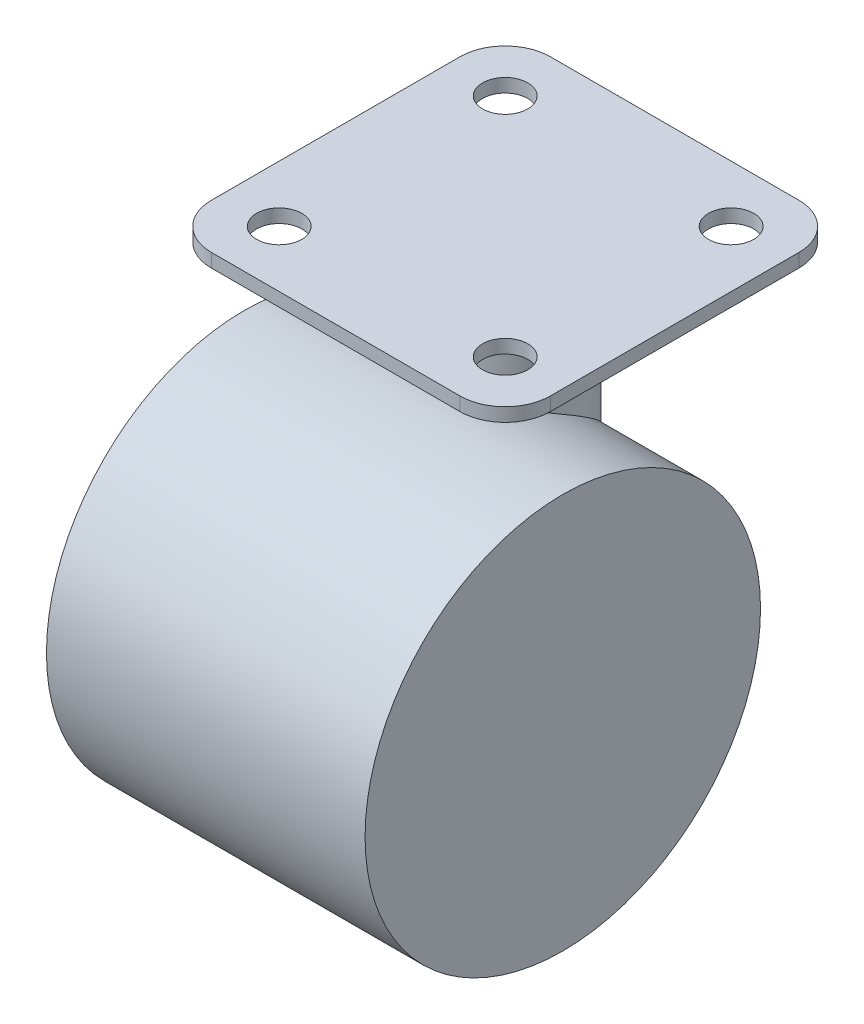
SolidWorks part; units mm, degrees
ref_plane "Спереди" through (0, 0, 0) normal (0, 0, 1) x (1, 0, 0)
ref_plane "Сверху" through (0, 0, 0) normal (0, 1, 0) x (1, 0, 0)
ref_plane "Справа" through (0, 0, 0) normal (1, 0, 0) x (0, 0, -1)
sketch "Эскиз1" plane through (0, 0, 0) normal (0, 1, 0) x (1, 0, 0)
  line L1 (-15, -15) -> (15, -15)
  line L2 (-15, -15) -> (-15, 15)
  line L3 (-15, 15) -> (15, 15)
  line L4 (15, -15) -> (15, 15)
  line L5 (-15, -15) -> (15, 15) construction
  line L6 (-15, 15) -> (15, -15) construction
  point P0 (0, 0)
  dimension "D2" = 30
extrude "основание" add sketch "Эскиз1" against normal mid plane 1.2
sketch "Эскиз7" plane through (0, 0.6, 0) normal (0, 1, 0) x (1, 0, 0)
  line L1 (-10, -10) -> (10, -10) construction
  line L2 (-10, -10) -> (-10, 10) construction
  line L3 (-10, 10) -> (10, 10) construction
  line L4 (10, -10) -> (10, 10) construction
  line L5 (-10, -10) -> (10, 10) construction
  line L6 (-10, 10) -> (10, -10) construction
  circle A0 centre (-10, 10) radius 2
  circle A1 centre (10, 10) radius 2
  circle A2 centre (10, -10) radius 2
  circle A3 centre (-10, -10) radius 2
  point P0 (0, 0)
  dimension "D1" = 4
  dimension "D2" = 20
  dimension "D3" = 20
extrude "крепженые отверстия" cut sketch "Эскиз7" against normal through all
fillet "Скругление4" radius 4 4 edges at (15, 0, -15) (15, 0, 15) (-15, 0, 15) (-15, 0, -15)
sketch "Эскиз9" plane through (0, 0, 0) normal (1, 0, 0) x (0, 0, -1)
  line L1 (-11, 0.6) -> (11, 0.6) construction
  circle A0 centre (-9, -25.9) radius 17.5
  point P5 (-9, -43.4)
  dimension "D1" = 35
  dimension "D3" = 9
  dimension "D2" = 44
extrude "Колесо" add sketch "Эскиз9" along normal mid plane 28.2 separate body
sketch "Эскиз8" plane through (0, -0.6, 0) normal (0, -1, 0) x (1, 0, 0)
  circle A0 centre (0, 0) radius 6
  dimension "D1" = 12
extrude "Штырь" add sketch "Эскиз8" along normal up to surface (16.2861 mm away) up to face at (14.1, -25.9, -8.5)
